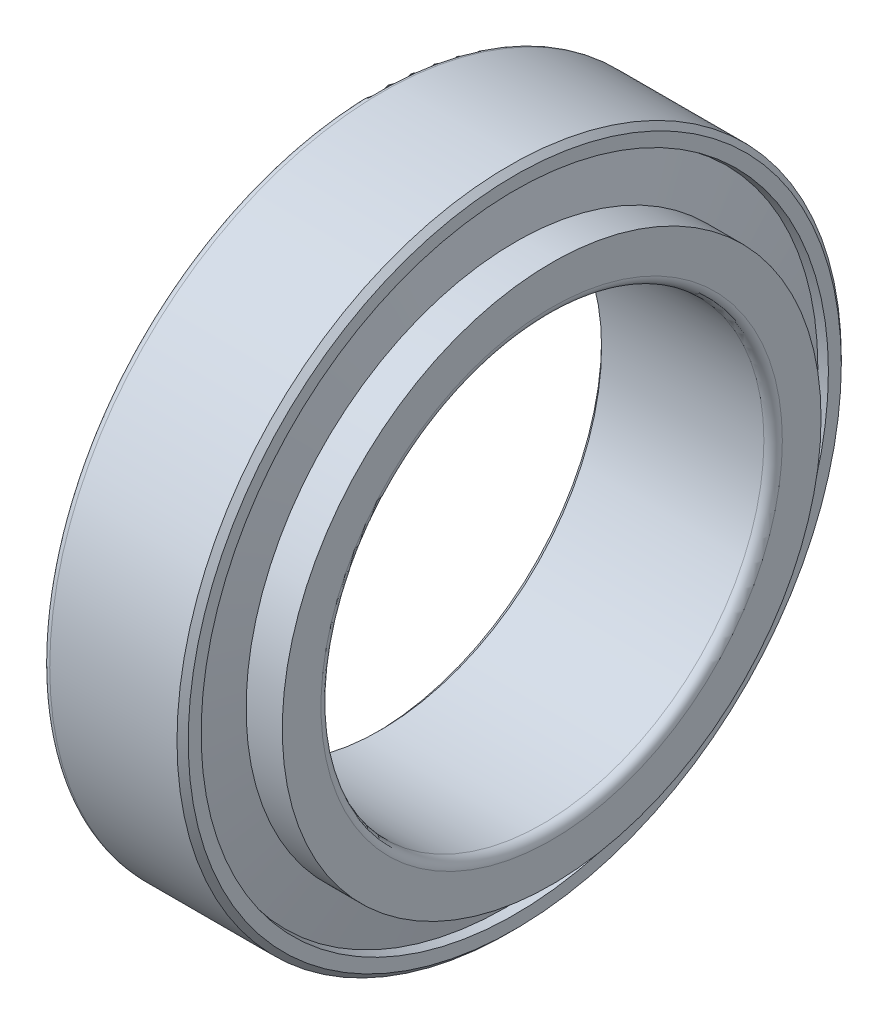
SolidWorks part; units mm, degrees
revolve "OuterRace" add sketch "OutRacSke" angle 360 about L5 other way angle 28.04 reverse direction yes
sketch "OutRacSke" plane through (0, 0, 0) normal (0, 0, 1) x (1, 0, 0)
  line L0 (-10, 84.9816) -> (-48, 77.3885)
  line L1 (-48, 77.3885) -> (-48, 88)
  line L2 (-46, 90) -> (-11.52, 90)
  line L3 (-11.52, 90) -> (-10, 88.48)
  line L4 (-10, 88.48) -> (-10, 84.9816)
  line L5 (-42.5, 0) -> (42.5, 0) construction
  arc A0 (-48, 88) -> (-46, 90) centre (-46, 88) cw
  dimension "D8" = 45
  dimension "Tangle" = 11.3
ref_plane "Plane1" through (0, 0, 0) normal (0, 0, 1) x (1, 0, 0)
ref_plane "Plane2" through (0, 0, 0) normal (0, 1, 0) x (1, 0, 0)
ref_plane "Plane3" through (0, 0, 0) normal (1, 0, 0) x (0, 0, -1)
sketch "Clipboard" plane through (0, 0, 0) normal (0, 0, 1) x (1, 0, 0)
  line L0 (0, 0) -> (10, 0) construction
  line L1 (0, 0) -> (154.6827, -5.4016)
  line L2 (0, 0) -> (119.9269, 4.1879)
  line L3 (0, 0) -> (179.8903, -6.2819)
  line L4 (0, 0) -> (-34.1948, -0.5969)
  line L5 (0, 0) -> (-13.5, 48)
  dimension "Roller_diameter" = 13.5
  dimension "cyl_len" = 34.2
sketch "RolDetSke" plane through (0, 0, 0) normal (0, 0, 1) x (1, 0, 0)
  line L0 (-44.6774, 71.5579) -> (-46, 78.1771)
  line L1 (-44.6774, 71.5579) -> (-11.1403, 78.2593)
  line L2 (-12.463, 84.8784) -> (-11.1403, 78.2593)
  line L4 (-52.52, 69.9908) -> (-2.9769, 79.8905) construction
  line L5 (-12.463, 84.8784) -> (-46, 78.1771)
  line L9 (-10, 84.9816) -> (-48, 77.3885) construction
  dimension "Roller_diameter" = 13.5
  dimension "dy" = 78.1771
  dimension "D2" = 46
  dimension "cyl_len" = 34.2
revolve "RollerDetailed" [suppressed] add sketch "RolDetSke" angle 360 about L4 reverse direction yes
sketch "RolSimSke" plane through (0, 0, 0) normal (0, 0, 1) x (1, 0, 0)
  line L0 (0, 0) -> (-32, 0) construction
  line L1 (-46, 78.1771) -> (-12.463, 84.8784)
  line L2 (-46, 78.1771) -> (-43.3547, 64.9388)
  line L3 (-43.3547, 64.9388) -> (-9.8177, 71.6401)
  line L4 (-12.463, 84.8784) -> (-9.8177, 71.6401)
  dimension "Roller_diameter" = 13.5
  dimension "dy" = 78.1771
  dimension "dx" = 46
  dimension "Tangle" = 11.3
revolve "RollersSimplified" add sketch "RolSimSke" angle 360 about L0
ref_axis "Axis1" through (-50, 0, 0) along (1, 0, 0)
pattern_circular "RollersDetailed" [suppressed] count 2 every 180 about axis through (-50, 0, 0) along (1, 0, 0)
sketch "InsRacSke" plane through (0, 0, 0) normal (0, 0, 1) x (1, 0, 0)
  line L0 (-43.4764, 65.6138) -> (-48, 65.6138)
  line L1 (-48, 88) -> (-48, -88) construction
  line L2 (-48, 65.6138) -> (-48, 61.52)
  line L3 (-48, 61.52) -> (-46.48, 60)
  line L4 (-46.48, 60) -> (-2.5, 60)
  line L5 (0, 62.5) -> (0, 72.9901)
  line L6 (0, 72.9901) -> (-9.8045, 72.9901)
  line L7 (-9.8045, 72.9901) -> (-9.8045, 71.6401)
  line L8 (-9.8045, 71.6401) -> (-43.3415, 64.9388)
  line L9 (-43.3415, 64.9388) -> (-43.4764, 65.6138)
  line L10 (-42.5, 0) -> (42.5, 0) construction
  arc A0 (-2.5, 60) -> (0, 62.5) centre (-2.5, 62.5) ccw
  dimension "Tangle" = 11.3
  dimension "cyl_len" = 34.2
  dimension "dy" = 64.9388
  dimension "dx" = 43.3415
  dimension "D11" = 45
  dimension "D2" = 48
revolve "InnerRace" add sketch "InsRacSke" angle 360 about L10 reverse direction yes
sketch "CagSpiSke" plane through (0, 0, 0) normal (0, 0, 1) x (1, 0, 0)
  line L3 (-9.4635, 78.2054) -> (-44.6774, 71.169)
  line L4 (-45.3836, 70.1101) -> (-45.0309, 68.345)
  line L6 (-42.5, 0) -> (42.5, 0) construction
  arc A1 (-44.6774, 71.169) -> (-45.3836, 70.1101) centre (-44.501, 70.2864) ccw
  dimension "Tangle" = 11.3
  dimension "radius" = 0.9
  dimension "dx" = 44.6774
  dimension "dy" = 71.169
  dimension "offset" = 2.7
revolve "CageSpine" [suppressed] add sketch "CagSpiSke" angle 0.001 about L6 wall 2.25
equation "\"OD@OutRacSke\" = \"Race_OD@Clipboard\""
equation "\"cup_SID@OutRacSke\" = \"Race_ID@Clipboard\""
equation "\"chamfer@OutRacSke\" = \"cup_width@OutRacSke\" / 25"
equation "\"offset@OutRacSke\" = \"OA_width@Clipboard\""
equation "\"D2@RolDetSke\" = \"offset@OutRacSke\" - \"cup_radius@OutRacSke\""
equation "\"dy@RolDetSke\" =  ( ( \"Race_ID@Clipboard\" / 2 ) + ( \"cup_radius@OutRacSke\" ) * tan(\"Tangle@OutRacSke\" * 3.141592654/180) ) * 1.005"
equation "\"cyl_len@RolDetSke\" = \"cyl_len@Clipboard\""
equation "\"Roller_diameter@RolDetSke\" = \"Roller_diameter@Clipboard\""
equation "\"dx@RolSimSke\" = \"offset@OutRacSke\" - \"cup_radius@OutRacSke\""
equation "\"dy@RolSimSke\" =  ( ( \"Race_ID@Clipboard\" / 2 ) + ( \"cup_radius@OutRacSke\" ) * tan(\"Tangle@OutRacSke\" * 3.141592654/180) ) * 1.005"
equation "\"Cyl_Len@RolSimSke\" = \"cyl_len@Clipboard\""
equation "\"Roller_diameter@RolSimSke\" = \"Roller_diameter@Clipboard\""
equation "\"Bore@InsRacSke\" = \"Bore@Clipboard\""
equation "\"Tangle@InsRacSke\" = \"Tangle@OutRacSke\""
equation "\"cyl_len@InsRacSke\" = \"cyl_len@Clipboard\""
equation "\"chamfer@InsRacSke\" = \"chamfer@OutRacSke\""
equation "\"D2@InsRacSke\" = \"OA_width@Clipboard\""
equation "\"dx@InsRacSke\" = \"offset@OutRacSke\" - \"cup_radius@OutRacSke\" -  (  \"Roller_diameter@Clipboard\" * 1.005 )  * sin(\"Tangle@InsRacSke\" * 3.141592654/180)"
equation "\"dy@InsRacSke\" = ( ( \"Race_ID@Clipboard\" / 2 ) + ( \"cup_radius@OutRacSke\" ) * tan(\"Tangle@OutRacSke\" * 3.141592654/180) ) * 1.005 -  ( \"Roller_diameter@Clipboard\" )  * cos(\"Tangle@InsRacSke\" * 3.141592654/180) "
equation "\"front_groove@InsRacSke\" = \"Groove_dp@InsRacSke\" / 2"
equation "\"Tangle@CagSpiSke\" = \"Tangle@OutRacSke\""
equation "\"dx@CagSpiSke\" = ( \"offset@OutRacSke\" - \"cup_radius@OutRacSke\" ) -  (  \"Roller_diameter@Clipboard\" / 2  )  * sin(\"Tangle@InsRacSke\" * 3.141592654/180)"
equation "\"dy@CagSpiSke\" = ( ( \"Race_ID@Clipboard\" / 2 ) + ( \"cup_radius@OutRacSke\" ) * tan(\"Tangle@OutRacSke\" * 3.141592654/180) )  -  ( \"Roller_diameter@Clipboard\" / 2 )  * cos(\"Tangle@InsRacSke\" * 3.141592654/180) "
equation "\"length@CagSpiSke\" = \"cyl_len@Clipboard\" * 1.05"
equation "\"offset@CagSpiSke\" = \"Roller_diameter@Clipboard\" / 5"
equation "\"radius@CagSpiSke\" = \"offset@CagSpiSke\" / 3"
equation "\"D3@CageSpine\" = \"Roller_diameter@Clipboard\" / 6"
equation "\"Max_count@Clipboard\" = int( 3.14159265 / atn(( \"Roller_diameter@Clipboard\" / 2) / sqr( \"dy@CagSpiSke\"  *  \"dy@CagSpiSke\" - ( \"Roller_diameter@Clipboard\" / 2) *  ( \"Roller_diameter@Clipboard\" / 2))))"
equation "\"Max_count@Clipboard\" = ((sgn( \"Max_count@Clipboard\" - \"Count@Clipboard\" )-1)*( \"Max_count@Clipboard\" - \"Count@Clipboard\" ))/-2+ \"Count@Clipboard\""
equation "\"Count@RollersDetailed\" = int( \"Show_count@Clipboard\" ) "
equation "\"Count@RollersDetailed\" = ((sgn( \"Count@RollersDetailed\" - \"Max_count@Clipboard\" )-1)*( \"Count@RollersDetailed\" - \"Max_count@Clipboard\" ))/-2+ \"Max_count@Clipboard\""
equation "\"Count@RollersDetailed\" = ((sgn( \"Count@RollersDetailed\" - \"Min_count@Clipboard\" )+1)*( \"Count@RollersDetailed\" - \"Min_count@Clipboard\"))/2 +\"Min_count@Clipboard\""
equation "\"Angle@RollersDetailed\" = 360.0 / \"Max_count@Clipboard\""
equation "\"Angle@CageSpine\" =  \"Angle@RollersDetailed\" * ( \"Count@RollersDetailed\" -1 + int( \"Count@RollersDetailed\" / \"Max_count@Clipboard\" ) )  + 0.001 -  int( \"Count@RollersDetailed\" / \"Max_count@Clipboard\" ) * 0.001"
equation "\"Angle@CageSpine\" =  \"Angle@CageSpine\" * int( \"Min_count@Clipboard\" / 2) + int(1 / \"Min_count@Clipboard\")  * 0.001"
equation "\"Tangle@RolSimSke\" = \"Tangle@OutRacSke\""
